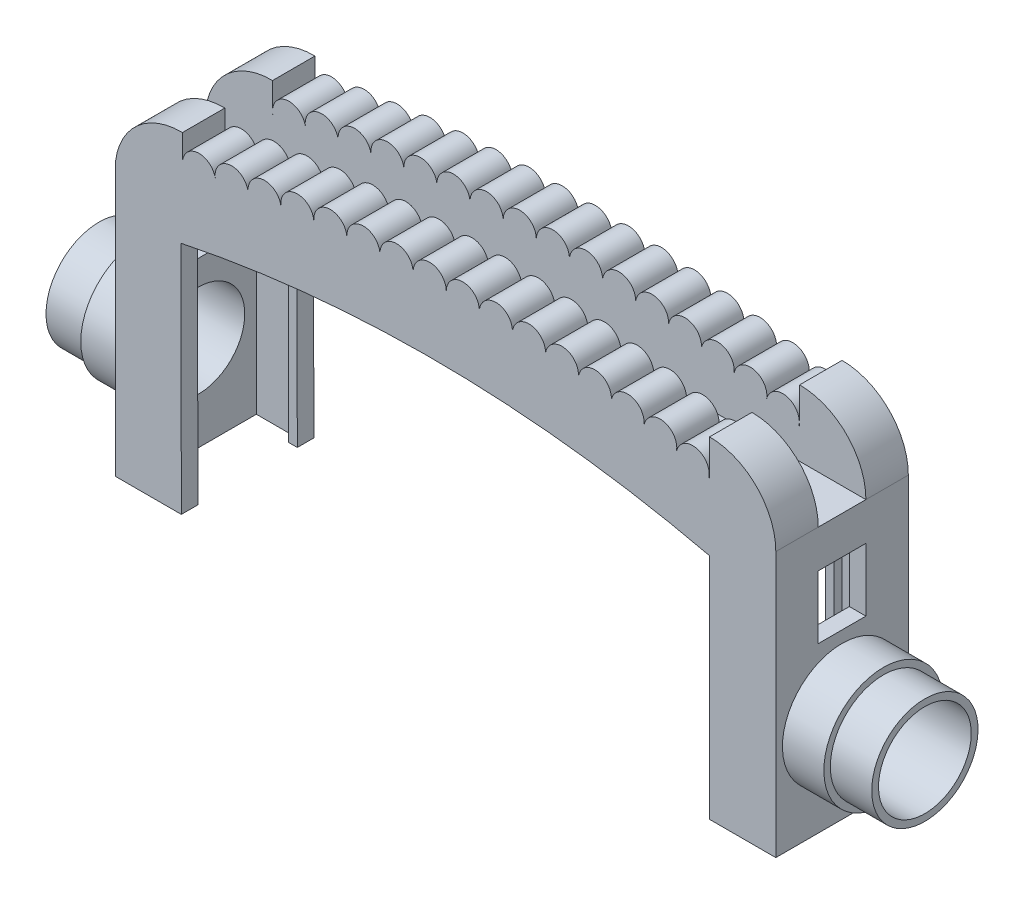
SolidWorks part; units mm, degrees
material "PVC 0.007 Plasticized"
ref_plane "Front Plane" through (0, 0, 0) normal (0, 0, 1) x (1, 0, 0)
ref_plane "Top Plane" through (0, 0, 0) normal (0, 1, 0) x (1, 0, 0)
ref_plane "Right Plane" through (0, 0, 0) normal (1, 0, 0) x (0, 0, -1)
ref_axis "X-Axis" through (-88.99, 0, 0) along (1, 0, 0)
ref_axis "Y-Axis" through (0, 55, 0) along (0, -1, 0)
ref_axis "Z-Axis" through (0, 0, 55) along (0, 0, -1)
sketch "Sketch1" plane through (0, 0, 0) normal (0, 0, 1) x (1, 0, 0)
  line L0 (25.2235, -24.9543) -> (31.5735, -24.9543)
  line L1 (31.5735, -24.9543) -> (31.5735, 0.4457)
  line L2 (25.2235, 6.7957) -> (25.2235, 3.3687)
  line L3 (25.2235, -24.9543) -> (25.2235, -3.0716)
  line L5 (0.0026, 6.4934) -> (0.2298, 25.4294) construction
  line L6 (-25.2973, 6.7948) -> (-25.2973, 3.9727)
  line L9 (-25.4, -24.9543) -> (-25.4407, -2.4636)
  line L10 (-25.4, -24.9543) -> (-31.7044, -24.9543)
  line L12 (-31.7044, 1.2051) -> (-31.7044, -24.9543)
  arc A0 (31.5735, 0.4457) -> (25.2235, 6.7957) centre (25.2235, 0.4457) ccw
  arc A3 (3.1579, 6.1919) -> (-0.0159, 6.2703) centre (1.5715, 6.2515) ccw
  arc A4 (9.4941, 5.7905) -> (6.3286, 6.0319) centre (7.9129, 5.9315) ccw
  arc A5 (12.6524, 5.4678) -> (9.4941, 5.7905) centre (11.0754, 5.6495) ccw
  arc A6 (15.8139, 5.1861) -> (12.6524, 5.4678) centre (14.2295, 5.2862) ccw
  arc A7 (18.9297, 4.5814) -> (15.8139, 5.1861) centre (17.364, 4.8435) ccw
  arc A8 (22.0499, 3.9975) -> (18.9297, 4.5814) centre (20.4954, 4.3194) ccw
  arc A9 (25.1645, 3.3818) -> (22.0499, 3.9975) centre (23.6044, 3.6756) ccw
  arc A10 (6.3286, 6.0319) -> (3.1579, 6.1919) centre (4.7443, 6.1323) ccw
  arc A11 (-3.1906, 6.2673) -> (-0.0159, 6.2703) centre (-1.6033, 6.2892) cw
  arc A12 (-6.3642, 6.1826) -> (-3.1906, 6.2673) centre (-4.778, 6.2453) cw
  arc A13 (-9.5346, 6.0164) -> (-6.3642, 6.1826) centre (-7.9505, 6.1199) cw
  arc A14 (-12.6997, 5.7689) -> (-9.5346, 6.0164) centre (-11.1187, 5.913) cw
  arc A15 (-15.8519, 5.3981) -> (-12.6997, 5.7689) centre (-14.2806, 5.6247) cw
  arc A16 (-19, 4.9882) -> (-15.8519, 5.3981) centre (-17.4231, 5.1714) cw
  arc A17 (-22.142, 4.5397) -> (-19, 4.9882) centre (-20.5769, 4.8051) cw
  arc A18 (-25.2669, 3.9787) -> (-22.142, 4.5397) centre (-23.7072, 4.2742) cw
  arc A19 (-31.7044, 1.2051) -> (-25.2973, 6.7948) centre (-25.4, 0.4457) cw
  arc A20 (-25.2973, 3.9727) -> (-25.2669, 3.9787) centre (-1.4828, -117.2774) cw
  arc A22 (-25.4407, -2.4636) -> (25.2235, -3.0716) centre (-1.4828, -117.2774) cw
  arc A37 (25.1645, 3.3818) -> (25.2235, 3.3687) centre (-1.4828, -117.2774) cw
  dimension "D4" = 3.175
  dimension "D6" = 3.175
  dimension "D1" = 31.75
  dimension "D2" = 6.35
extrude "Boss-Extrude1" add sketch "Sketch1" against normal blind 12.7
sketch "Sketch3" plane through (0, 0, 0) normal (1, 0, 0) x (0, 0, -1)
  line L0 (12.7, 0.4457) -> (0, 0.4457) construction
  line L1 (4.0652, 0.4457) -> (8.6348, 0.4457)
  line L2 (4.0652, 0.4457) -> (4.0652, 13.0566)
  line L3 (4.0652, 13.0566) -> (8.6348, 13.0566)
  line L4 (8.6348, 0.4457) -> (8.6348, 13.0566)
  line L6 (6.35, 31.4165) -> (6.35, -30.5252) construction
  line L7 (12.7, -24.9543) -> (12.7, 0.4457) construction
  point P10 (6.35, 0.4457)
  dimension "D1" = 6.35
extrude "Cut-Extrude1" cut sketch "Sketch3" against normal through all both and the other way through all
sketch "Sketch4" plane through (31.5735, 0, 0) normal (1, 0, 0) x (0, 0, -1)
  line L0 (4.0652, 0.4457) -> (4.0652, 6.7957) construction
  line L1 (4.0652, -9.2251) -> (8.6348, -9.2251)
  line L2 (4.0652, -9.2251) -> (4.0652, -3.1859)
  line L3 (4.0652, -3.1859) -> (8.6348, -3.1859)
  line L4 (8.6348, -9.2251) -> (8.6348, -3.1859)
  line L5 (8.6348, 6.7957) -> (8.6348, 0.4457) construction
extrude "Cut-Extrude2" cut sketch "Sketch4" against normal blind 66.04
sketch "Sketch5" plane through (31.5735, 0, 0) normal (1, 0, 0) x (0, 0, -1)
  line L0 (6.35, -26.9034) -> (6.35, -5.1624) construction
  line L1 (12.7, -24.9543) -> (12.7, 0.4457) construction
  line L3 (6.35, -21.7793) -> (19.8009, -21.7793) construction
  line L4 (12.7, -24.9543) -> (0, -24.9543) construction
  circle A0 centre (6.35, -16.0643) radius 5.715
  dimension "D2" = 11.43
  dimension "D1" = 6.35
  dimension "D3" = 3.175
extrude "Boss-Extrude2" add sketch "Sketch5" along normal blind 3.9688
sketch "Sketch6" plane through (35.5422, 0, 0) normal (1, 0, 0) x (0, 0, -1)
  circle A0 centre (6.35, -16.0643) radius 4.445
  dimension "D1" = 8.89
sketch "Sketch7" plane through (35.5422, 0, 0) normal (1, 0, 0) x (0, 0, -1)
  circle A0 centre (6.35, -16.0643) radius 5.0932
extrude "Boss-Extrude3" add sketch "Sketch7" along normal blind 3.9688
sketch "Sketch9" plane through (-31.7044, 0, 0) normal (-1, 0, 0) x (0, 0, 1)
  circle A0 centre (-6.35, -16.0643) radius 5.715
  dimension "D1" = 11.43
extrude "Boss-Extrude4" add sketch "Sketch9" along normal blind 3.9688
sketch "Sketch10" plane through (-35.6732, 0, 0) normal (-1, 0, 0) x (0, 0, 1)
  circle A0 centre (-6.35, -16.0643) radius 5.08
  dimension "D1" = 10.16
extrude "Boss-Extrude5" add sketch "Sketch10" along normal blind 3.9688
sketch "Sketch8" plane through (39.511, 0, 0) normal (1, 0, 0) x (0, 0, -1)
  circle A0 centre (6.35, -16.0643) radius 4.445
  dimension "D1" = 8.89
extrude "Cut-Extrude4" cut sketch "Sketch8" against normal through all
sketch "Sketch11" plane through (-25.445, -0.046, 0) normal (1, 0.0018, 0) x (0, 0, -1)
  line L2 (1.5875, -2.4176) -> (1.5875, -26.7627)
  line L3 (1.5875, -26.7627) -> (11.1125, -26.7627)
  line L4 (11.1125, -2.4176) -> (11.1125, -26.7627)
  line L5 (12.7, -25.0114) -> (12.7, 0.3886) construction
  line L6 (0, -25.0114) -> (0, 0.3886) construction
  line L7 (1.5875, -2.4176) -> (11.1125, -2.4176)
  line L8 (12.7, -2.4176) -> (0, -2.4176) construction
  dimension "D1" = 1.5875
  dimension "D2" = 1.5875
extrude "Cut-Extrude5" cut sketch "Sketch11" against normal offset from surface (4.6763 mm away) 1.5875 up to face at (-31.7044, -16.0643, -0.635)
sketch "Sketch13" plane through (25.2235, 0, 0) normal (-1, 0, 0) x (0, 0, 1)
  line L1 (-11.1125, -2.4721) -> (-1.5875, -2.4721)
  line L2 (-11.1125, -2.4721) -> (-11.1125, -24.9543)
  line L3 (-11.1125, -24.9543) -> (-1.5875, -24.9543)
  line L4 (-1.5875, -2.4721) -> (-1.5875, -24.9543)
extrude "Cut-Extrude6" cut sketch "Sketch13" against normal offset from surface (4.7625 mm away) 1.5875 up to face at (31.5735, -10.3493, -6.35)
sketch "Sketch14" plane through (0, -24.9543, 0) normal (0, -1, 0) x (1, 0, 0)
  line L1 (-30.1169, -0.7938) -> (-26.2344, -0.7938)
  line L2 (-30.1169, -0.7938) -> (-30.1169, -11.9063)
  line L3 (-30.1169, -11.9063) -> (-26.2344, -11.9063)
  line L5 (-25.4, -1.5875) -> (-30.1169, -1.5875) construction
  line L6 (-30.1169, -11.1125) -> (-25.4, -11.1125) construction
  line L7 (-26.2344, -0.7938) -> (-26.2344, -11.9063)
  line L8 (-25.4407, -11.1125) -> (-25.4407, -1.5875) construction
  dimension "D1" = 0.7937
  dimension "D2" = 0.7937
  dimension "D3" = 0.7937
extrude "Cut-Extrude7" cut sketch "Sketch14" against normal up to surface (22.4893 mm away) up to face at (-27.7788, -2.4678, -6.35)
sketch "Sketch15" plane through (0, -24.9543, 0) normal (0, -1, 0) x (1, 0, 0)
  line L0 (25.2235, -1.5875) -> (25.2235, -11.1125) construction
  line L1 (26.0172, -0.7937) -> (29.9631, -0.7937)
  line L2 (26.0172, -0.7937) -> (26.0172, -11.9062)
  line L3 (26.0172, -11.9062) -> (29.9631, -11.9062)
  line L4 (29.9631, -0.7937) -> (29.9631, -11.9062)
  line L5 (25.2235, 0) -> (31.5735, 0) construction
  line L6 (25.2235, -12.7) -> (31.5735, -12.7) construction
  dimension "D1" = 0.7937
  dimension "D2" = 0.7937
  dimension "D3" = 0.7937
extrude "Cut-Extrude8" cut sketch "Sketch15" against normal up to surface (22.4823 mm away) up to face at (27.6047, -2.4721, -6.35)
